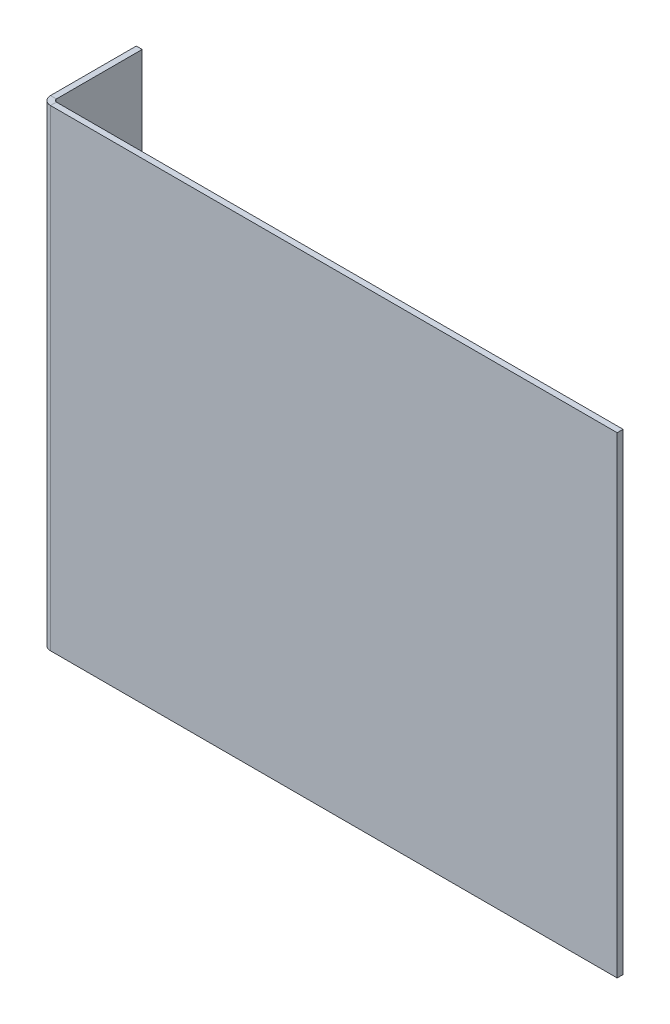
SolidWorks part; units mm, degrees
note: The reader was unsure of these and kept them because the rebuilt part matched: flange length of "Edge-Flange1".
ref_plane "Front Plane" through (0, 0, 0) normal (0, 0, 1) x (1, 0, 0)
ref_plane "Top Plane" through (0, 0, 0) normal (0, 1, 0) x (1, 0, 0)
ref_plane "Right Plane" through (0, 0, 0) normal (1, 0, 0) x (0, 0, -1)
sketch "Sketch1" plane through (0, 0, 0) normal (0, 0, 1) x (1, 0, 0)
  line L1 (-76.2, 63.5) -> (76.2, 63.5)
  line L2 (-76.2, 63.5) -> (-76.2, -63.5)
  line L3 (-76.2, -63.5) -> (76.2, -63.5)
  line L4 (76.2, 63.5) -> (76.2, -63.5)
  line L5 (-76.2, 63.5) -> (76.2, -63.5) construction
  line L6 (-76.2, -63.5) -> (76.2, 63.5) construction
  point P0 (0, 0)
  dimension "D1" = 127
  dimension "D2" = 152.4
base flange "Base-Flange1" sketch "Sketch1" thickness 1.5875 reverse thickness direction no parameters "D1"=0.7366
edge flange "Edge-Flange1" sketch "Sketch8" flange angle 90 flange length 25.4 flange position bend outside bend radius 0.7366 thickness 1.5875 relief rectangular parameters "D6"=10
sketch "Sketch8" plane through (-76.2, 0, -1.5875) normal (1, 0, 0) x (0, -1, 0)
  line L2 (-63.5, 0) -> (-63.5, 23.8125)
  line L3 (-63.5, 23.8125) -> (63.5, 23.8125)
  line L4 (63.5, 23.8125) -> (63.5, 0)
  line L6 (63.5, 0) -> (-63.5, 0) construction
  line L7 (63.5, 0) -> (-63.5, 0)
bend "EdgeBend1" bend radius 0.7366 bend angle 90 parameters "D5"=1
sketch "Bend-Lines1" [suppressed] plane through (0, 0, 0) normal (0, 1, 0) x (1, 0, 0)
sketch "Bounding-Box1" [suppressed] plane through (0, 0, 0) normal (0, 1, 0) x (1, 0, 0)
sheet metal parameters "Sheet-Metal1" thickness 1.5875 parameters "D1"=0.7366
flat pattern "Flat-Pattern1" [suppressed]
sketch "Bend-Lines2" plane through (0, 0, 0) normal (0, 1, 0) x (1, 0, 0)
sketch3d "Bounding-Box2" [suppressed]
  line L0 (76.2, -63.5, 0) -> (-76.2, -63.5, 0) construction
  line L1 (76.2, 63.5, 0) -> (-76.2, 63.5, 0) construction
  line L2 (76.2, -63.5, 0) -> (76.2, 63.5, 0) construction
  line L3 (-76.2, -63.5, 0) -> (-76.2, 63.5, 0) construction
sheet metal parameters "Sheet-Metal2" thickness 1.5875 parameters "D1"=0.7366
flat pattern "Flat-Pattern1"
sketch "Bend-Lines2" plane through (0, 0, 0) normal (0, 0, 1) x (1, 0, 0)
  line L0 (-77.4019, 63.5) -> (-77.4019, -63.5) construction
  line L1 (-77.4019, 63.5) -> (-77.4019, -63.5) construction
sketch3d "Bounding-Box2" [suppressed]
  line L0 (-101.6798, -63.5, 0) -> (76.2, -63.5, 0) construction
  line L1 (-101.6798, 63.5, 0) -> (76.2, 63.5, 0) construction
  line L2 (-101.6798, -63.5, 0) -> (-101.6798, 63.5, 0) construction
  line L3 (76.2, -63.5, 0) -> (76.2, 63.5, 0) construction
bend of the flat pattern "Flatten-<EdgeBend1>1"
